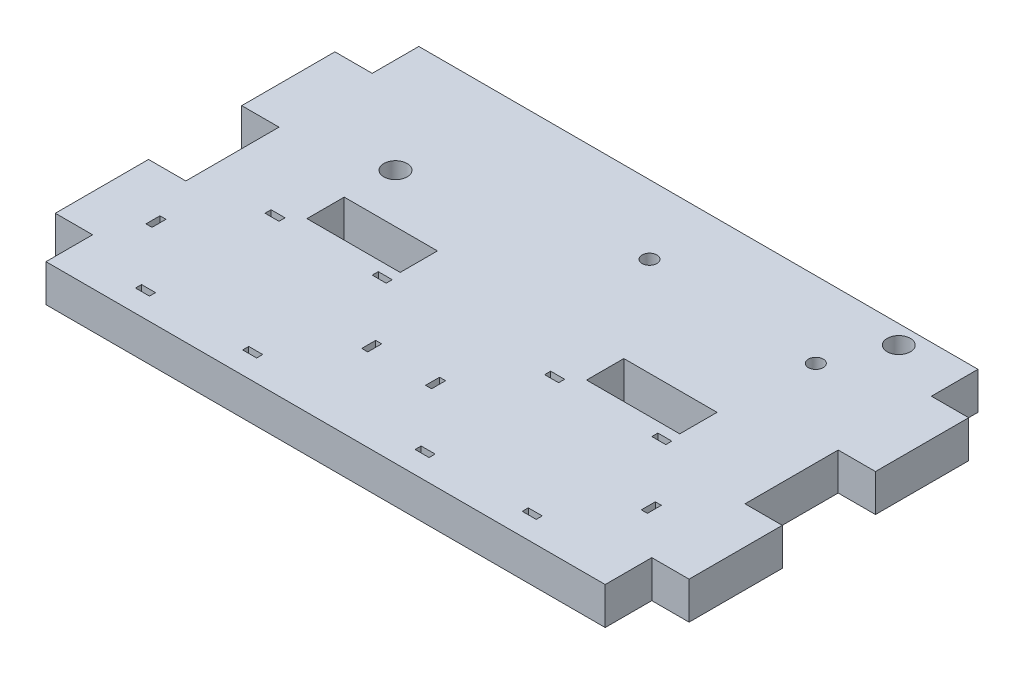
SolidWorks part; units mm, degrees
ref_plane "Front Plane" through (0, 0, 0) normal (0, 0, 1) x (1, 0, 0)
ref_plane "Top Plane" through (0, 0, 0) normal (0, 1, 0) x (1, 0, 0)
ref_plane "Right Plane" through (0, 0, 0) normal (1, 0, 0) x (0, 0, -1)
sketch "Sketch1" plane through (0, 0, 0) normal (0, 1, 0) x (1, 0, 0)
  line L0 (-66.0627, 0) -> (65.2437, 0) construction
  line L1 (-60, 40) -> (60, 40)
  line L2 (-60, 40) -> (-60, -40)
  line L3 (-60, -40) -> (60, -40)
  line L4 (60, 40) -> (60, -40)
  line L5 (27.5, -7.5) -> (27.5, -34) construction
  line L6 (45, 10) -> (-18.5, 10) construction
  line L7 (45, 10) -> (45, 35) construction
  line L8 (45, 35) -> (-18.5, 35) construction
  line L9 (-18.5, 10) -> (-18.5, 35) construction
  line L10 (5, -7.5) -> (50, -7.5) construction
  line L11 (5, -7.5) -> (5, -34) construction
  line L12 (5, -34) -> (50, -34) construction
  line L13 (50, -7.5) -> (50, -34) construction
  line L14 (5, -20.75) -> (50, -20.75) construction
  line L15 (40.5, -7.5) -> (37.5, -7.5)
  line L16 (14.5, -7.5) -> (17.5, -7.5)
  line L17 (14.5, -7.5) -> (14.5, -6.2)
  line L18 (14.5, -6.2) -> (17.5, -6.2)
  line L19 (17.5, -7.5) -> (17.5, -6.2)
  line L20 (5, -19.25) -> (3.7, -19.25)
  line L21 (5, -19.25) -> (5, -22.25)
  line L22 (5, -22.25) -> (3.7, -22.25)
  line L23 (3.7, -19.25) -> (3.7, -22.25)
  line L24 (37.5, -7.5) -> (37.5, -6.2)
  line L25 (40.5, -6.2) -> (37.5, -6.2)
  line L26 (40.5, -7.5) -> (40.5, -6.2)
  line L27 (50, -19.25) -> (51.3, -19.25)
  line L28 (51.3, -19.25) -> (51.3, -22.25)
  line L29 (50, -22.25) -> (51.3, -22.25)
  line L30 (50, -19.25) -> (50, -22.25)
  line L31 (37.5, -34) -> (37.5, -35.3)
  line L32 (40.5, -34) -> (37.5, -34)
  line L33 (40.5, -34) -> (40.5, -35.3)
  line L34 (40.5, -35.3) -> (37.5, -35.3)
  line L35 (14.5, -34) -> (17.5, -34)
  line L36 (17.5, -34) -> (17.5, -35.3)
  line L37 (14.5, -34) -> (14.5, -35.3)
  line L38 (14.5, -35.3) -> (17.5, -35.3)
  line L39 (-2.5, -65.1553) -> (-2.5, 67.8606) construction
  line L41 (-42, 14.5) -> (-60, 14.5) construction
  line L43 (-40, 4) -> (-24.847, 4) construction
  line L44 (-39.5, 12) -> (-39.5, 4) construction
  line L45 (68, 4) -> (40, 4) construction
  line L46 (-19.5, -35.3) -> (-22.5, -35.3)
  line L47 (-19.5, -34) -> (-19.5, -35.3)
  line L48 (-22.5, -34) -> (-22.5, -35.3)
  line L49 (-19.5, -34) -> (-22.5, -34)
  line L50 (-45.5, -35.3) -> (-42.5, -35.3)
  line L51 (-45.5, -34) -> (-45.5, -35.3)
  line L52 (-45.5, -34) -> (-42.5, -34)
  line L53 (-42.5, -34) -> (-42.5, -35.3)
  line L54 (-55, -19.25) -> (-55, -22.25)
  line L55 (-55, -22.25) -> (-56.3, -22.25)
  line L56 (-56.3, -19.25) -> (-56.3, -22.25)
  line L57 (-55, -19.25) -> (-56.3, -19.25)
  line L58 (-45.5, -7.5) -> (-45.5, -6.2)
  line L59 (-45.5, -6.2) -> (-42.5, -6.2)
  line L60 (-42.5, -7.5) -> (-42.5, -6.2)
  line L61 (-8.7, -19.25) -> (-8.7, -22.25)
  line L62 (-10, -22.25) -> (-8.7, -22.25)
  line L63 (-10, -19.25) -> (-10, -22.25)
  line L64 (-10, -19.25) -> (-8.7, -19.25)
  line L65 (-22.5, -7.5) -> (-22.5, -6.2)
  line L66 (-19.5, -6.2) -> (-22.5, -6.2)
  line L67 (-19.5, -7.5) -> (-19.5, -6.2)
  line L68 (-19.5, -7.5) -> (-22.5, -7.5)
  line L69 (-45.5, -7.5) -> (-42.5, -7.5)
  circle A0 centre (41.5, 23.7) radius 1.6
  circle A1 centre (4.3, 25.2) radius 1.6
  circle A2 centre (-39.5, 14.5) radius 2.5
  circle A3 centre (47, 36) radius 2.5
  point P4 (60, 0)
  point P6 (0, 40)
  point P33 (5, -20.75)
  point P87 (0, 0)
  dimension "D5" = 3.2
  dimension "D10" = 3.2
  dimension "D17" = 3
  dimension "D18" = 1.3
  dimension "D23" = 18
  dimension "D24" = 13
  dimension "D26" = 5
  dimension "D1" = 120
  dimension "D2" = 80
  dimension "D3" = 10
  dimension "D4" = 15
  dimension "D6" = 3.5
  dimension "D7" = 13.7
  dimension "D8" = 63.5
  dimension "D9" = 25
  dimension "D11" = 40.7
  dimension "D12" = 15.2
  dimension "D13" = 26.5
  dimension "D14" = 45
  dimension "D15" = 7.5
  dimension "D16" = 15
  dimension "D19" = 3
  dimension "D20" = 1.3
  dimension "D21" = 20
  dimension "D22" = 10
  dimension "D25" = 32
extrude "Boss-Extrude1" add sketch "Sketch1" along normal blind 8
sketch "Sketch2" plane through (0, 0, 0) normal (0, -1, 0) x (-1, 0, 0)
  line L1 (-7.4754, 25.2) -> (-5.8877, 22.45)
  line L2 (-5.8877, 22.45) -> (-2.7123, 22.45)
  line L3 (-2.7123, 22.45) -> (-1.1246, 25.2)
  line L4 (-1.1246, 25.2) -> (-2.7123, 27.95)
  line L5 (-2.7123, 27.95) -> (-5.8877, 27.95)
  line L6 (-5.8877, 27.95) -> (-7.4754, 25.2)
  line L7 (-44.6754, 23.7) -> (-43.0877, 20.95)
  line L8 (-43.0877, 20.95) -> (-39.9123, 20.95)
  line L9 (-39.9123, 20.95) -> (-38.3246, 23.7)
  line L10 (-38.3246, 23.7) -> (-39.9123, 26.45)
  line L11 (-39.9123, 26.45) -> (-43.0877, 26.45)
  line L12 (-43.0877, 26.45) -> (-44.6754, 23.7)
  circle A0 centre (-4.3, 25.2) radius 2.75 construction
  circle A1 centre (-41.5, 23.7) radius 2.75 construction
  dimension "D1" = 5.5
  dimension "D2" = 5.5
extrude "Cut-Extrude1" cut sketch "Sketch2" against normal blind 4
sketch "Sketch3" plane through (-60, 0, 0) normal (-1, 0, 0) x (0, 0, 1)
  line L0 (-40, 8) -> (-40, 0) construction
  line L1 (-30, 0) -> (-10, 0)
  line L2 (-30, 0) -> (-30, 8)
  line L3 (-30, 8) -> (-10, 8)
  line L4 (-10, 0) -> (-10, 8)
  line L5 (-40, 0) -> (40, 0) construction
  line L6 (0, 15.2289) -> (0, -7.9114) construction
  line L7 (10, 0) -> (10, 8)
  line L8 (30, 8) -> (10, 8)
  line L9 (30, 0) -> (30, 8)
  line L10 (30, 0) -> (10, 0)
  dimension "D1" = 20
  dimension "D2" = 20
extrude "Boss-Extrude2" add sketch "Sketch3" along normal blind 8
ref_plane "Plane1" through (0, 0, 0) normal (-1, 0, 0) x (0, 0, 1)
mirror "Mirror1" about plane through (0, 0, 0) normal (-1, 0, 0) of "Boss-Extrude2"
sketch "Sketch5" plane through (0, 0, 0) normal (0, -1, 0) x (-1, 0, 0)
  line L0 (74.0532, 0) -> (-79.4319, 0) construction
  line L1 (20, 4) -> (40, 4)
  line L2 (20, 4) -> (20, -4)
  line L3 (20, -4) -> (40, -4)
  line L4 (40, 4) -> (40, -4)
  line L5 (0, -4.4) -> (0, 4.4) construction
  point P7 (20, 0)
  dimension "D1" = 20
  dimension "D2" = 8
  dimension "D3" = 20
extrude "Cut-Extrude3" cut sketch "Sketch5" against normal up to next
mirror "Mirror2" about plane through (0, 0, 0) normal (-1, 0, 0) of "Cut-Extrude3"
